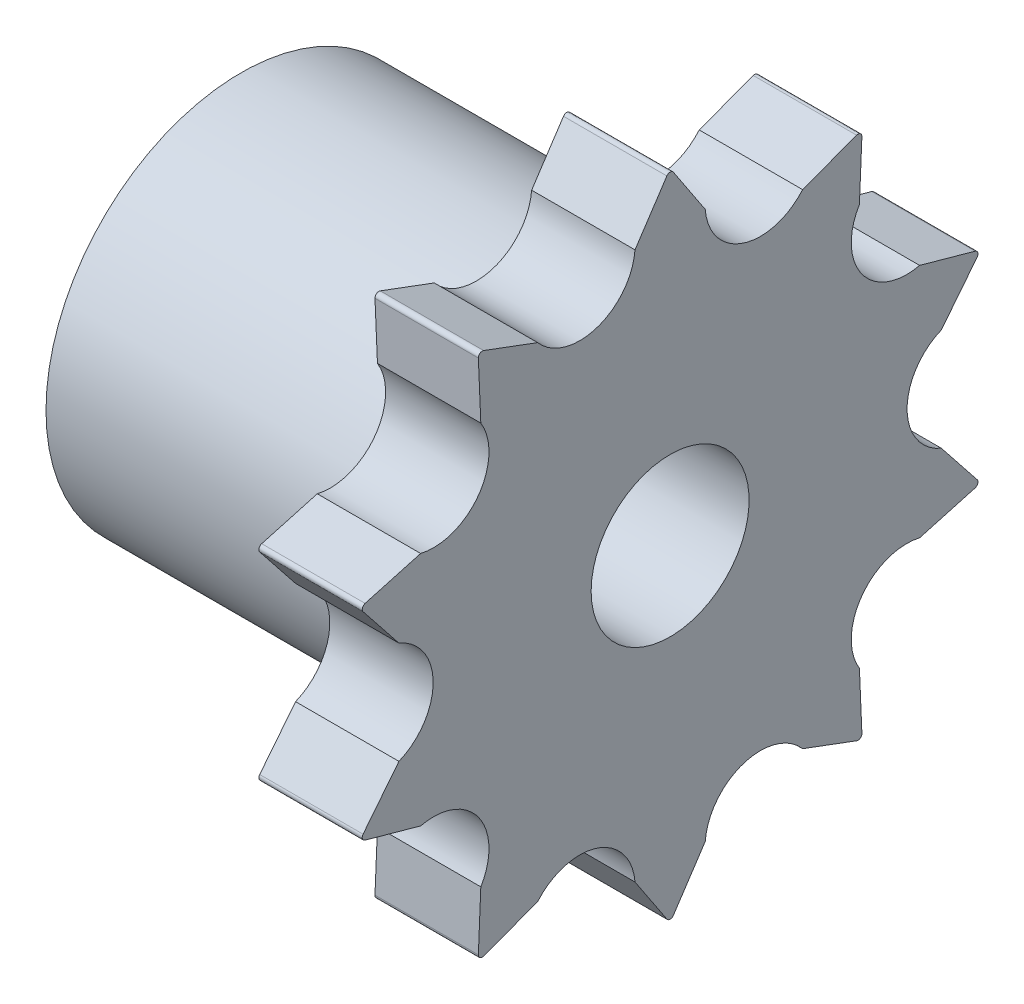
SolidWorks part; units mm, degrees
ref_plane "Front Plane" through (0, 0, 0) normal (0, 0, 1) x (1, 0, 0)
ref_plane "Top Plane" through (0, 0, 0) normal (0, 1, 0) x (1, 0, 0)
ref_plane "Right Plane" through (0, 0, 0) normal (1, 0, 0) x (0, 0, -1)
sketch "Sketch1" plane through (0, 0, 0) normal (1, 0, 0) x (0, 0, -1)
  line L0 (0, 0) -> (0, 16.75)
  line L1 (0, 0) -> (9.8454, 13.551)
  line L2 (0, 16.75) -> (1.8002, 14.035)
  line L3 (6.7932, 12.4127) -> (9.8454, 13.551)
  circle A0 centre (0, 0) radius 12.15
  circle A1 centre (0, 0) radius 16.75
  circle A2 centre (0, 0) radius 14.15 construction
  arc A3 (1.8002, 14.035) -> (6.7932, 12.4127) centre (4.6325, 14.2573) ccw
  dimension "D1" = 24.3
  dimension "D2" = 33.5
  dimension "D3" = 2.6
  dimension "D4" = 36
  dimension "D5" = 5.25
extrude "Boss-Extrude1" add sketch "Sketch1" along normal blind 5.3 contours L1 A0 L0 | A3 A0 L1 L3 | A3 L2 L0 A0 region at (0, 7.5775, -2.4621) region at (0, 13.656, -0.9718) region at (0, 11.6191, -7.2406)
pattern_circular "CirPattern1" count 10 over 360 about axis through (5.3, 0, 0) along (-1, 0, 0) of "Boss-Extrude1" reverse direction yes
fillet "Fillet1" radius 0.2 1 edges at (2.65, 16.75, 0)
fillet "Fillet3" radius 0.2 9 edges at (2.65, 13.551, 9.8454) (2.65, 5.176, 15.9302) (2.65, -5.176, 15.9302) (2.65, -13.551, 9.8454) (2.65, -16.75, 0) (2.65, -13.551, -9.8454) (2.65, -5.176, -15.9302) (2.65, 5.176, -15.9302) (2.65, 13.551, -9.8454)
sketch "Sketch2" plane through (0, 0, 0) normal (-1, 0, 0) x (0, 0, 1)
  circle A0 centre (0, 0) radius 10
  circle A1 centre (0, 0) radius 4.05
  dimension "D1" = 20
  dimension "D2" = 8.1
extrude "Boss-Extrude2" add sketch "Sketch2" along normal blind 16.7
extrude "Cut-Extrude1" cut sketch "Sketch2<2>" against normal through all both and the other way through all contours A1 region at (0, 0, 0)
sketch "Sketch2<2>" plane through (0, 0, 0) normal (-1, 0, 0) x (0, 0, 1) same geometry as "Sketch2"
